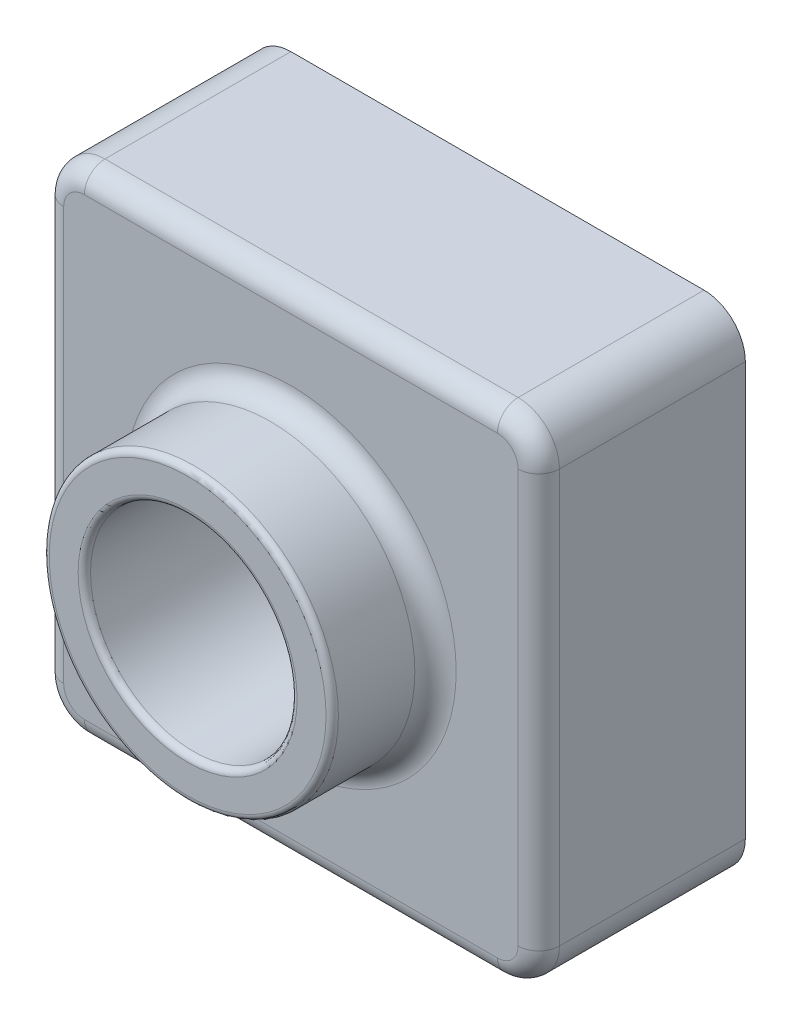
SolidWorks part; units mm, degrees
material "Chrome Stainless Steel"
ref_plane "Front Plane" through (0, 0, 0) normal (0, 0, 1) x (1, 0, 0)
ref_plane "Top Plane" through (0, 0, 0) normal (0, 1, 0) x (1, 0, 0)
ref_plane "Right Plane" through (0, 0, 0) normal (1, 0, 0) x (0, 0, -1)
sketch "Sketch1" plane through (0, 0, 0) normal (0, 0, 1) x (1, 0, 0)
  line L1 (-55.3709, 28.4866) -> (64.6291, 28.4866)
  line L2 (-55.3709, 28.4866) -> (-55.3709, -91.5134)
  line L3 (-55.3709, -91.5134) -> (64.6291, -91.5134)
  line L4 (64.6291, 28.4866) -> (64.6291, -91.5134)
  dimension "D1" = 120
  dimension "D2" = 120
extrude "Boss-Extrude1" add sketch "Sketch1" along normal blind 50
sketch "Sketch2" plane through (0, 0, 50) normal (0, 0, 1) x (1, 0, 0)
  line L0 (64.6291, 28.4866) -> (-55.3709, 28.4866) construction
  line L3 (64.6291, -91.5134) -> (64.6291, 28.4866) construction
  circle A0 centre (4.6291, -31.5134) radius 35
  dimension "D1" = 70
  dimension "D2" = 60
  dimension "D3" = 60
extrude "Boss-Extrude2" add sketch "Sketch2" along normal blind 25
sketch "Sketch3" plane through (0, 0, 75) normal (0, 0, 1) x (1, 0, 0)
  circle A0 centre (4.6291, -31.5134) radius 25
  dimension "D1" = 50
extrude "Cut-Extrude1" cut sketch "Sketch3" against normal through all
fillet "Fillet2" radius 10 4 edges at (-55.3709, -91.5134, 25) (64.6291, -91.5134, 25) (-55.3709, 28.4866, 25) (64.6291, 28.4866, 25)
fillet "Fillet3" radius 1.5 2 edges at (39.6291, -31.5134, 75) (29.6291, -31.5134, 75)
fillet "Fillet4" radius 5 9 edges at (-52.442, 25.5577, 50) (4.6291, 28.4866, 50) (61.7001, 25.5577, 50) (64.6291, -31.5134, 50) (61.7001, -88.5844, 50) (4.6291, -91.5134, 50) (-52.442, -88.5844, 50) (-55.3709, -31.5134, 50) (39.6291, -31.5134, 50)
shell "Shell1" thickness 2 removed face at (29.6291, -31.5134, 0)
